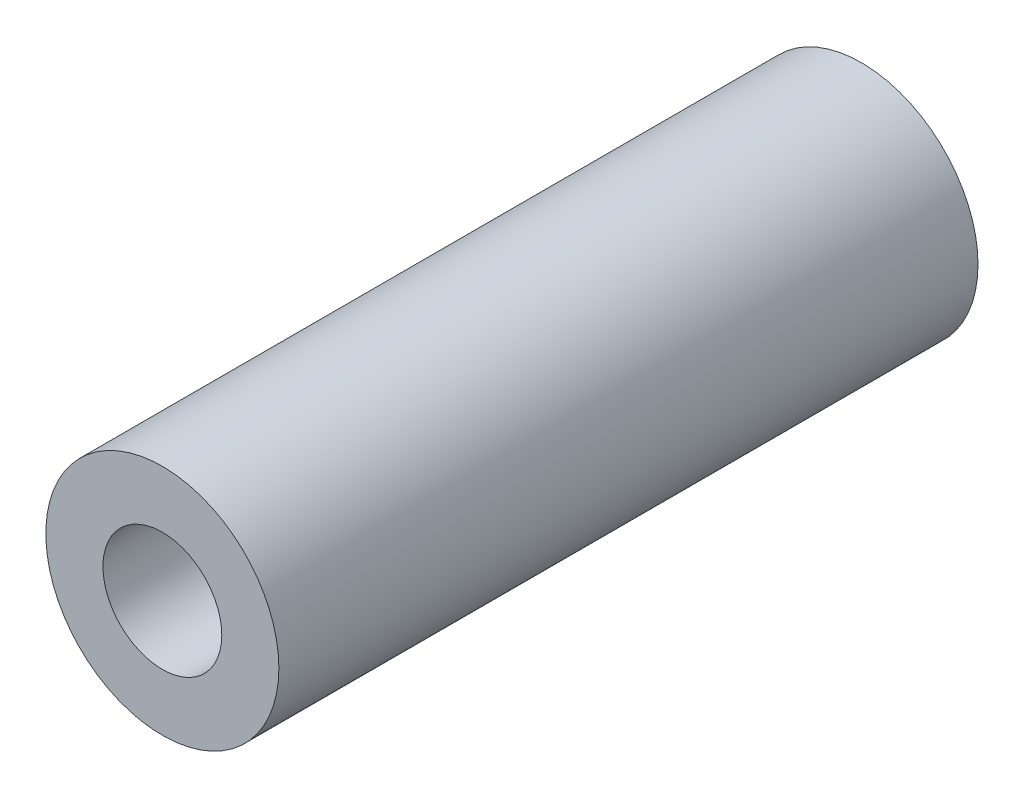
SolidWorks part; units mm, degrees
ref_plane "xy_plane" through (0, 0, 0) normal (0, 0, 1) x (1, 0, 0)
ref_plane "zx_plane" through (0, 0, 0) normal (0, 1, 0) x (1, 0, 0)
ref_plane "yz_plane" through (0, 0, 0) normal (1, 0, 0) x (0, 0, -1)
ref_axis "x_axis" through (-80.9, 0, 0) along (1, 0, 0)
ref_axis "y_axis" through (0, -50, 0) along (0, 1, 0)
ref_axis "z_axis" through (0, 0, -80.9) along (0, 0, 1)
ref_plane "xMid_plane" through (0, 0, 0) normal (1, 0, 0) x (0, 0, -1)
ref_plane "xMin_plane" through (-15, 0, 0) normal (1, 0, 0) x (0, 0, -1)
ref_plane "xMax_plane" through (15, 0, 0) normal (1, 0, 0) x (0, 0, -1)
ref_plane "yMid_plane" through (0, 0, 0) normal (0, 1, 0) x (1, 0, 0)
ref_plane "yMin_plane" through (0, -35, 0) normal (0, 1, 0) x (1, 0, 0)
ref_plane "yMax_plane" through (0, 35, 0) normal (0, 1, 0) x (1, 0, 0)
ref_plane "zMid_plane" through (0, 0, 0) normal (0, 0, 1) x (1, 0, 0)
ref_plane "zMin_plane" through (0, 0, -15) normal (0, 0, 1) x (1, 0, 0)
ref_plane "zMax_plane" through (0, 0, 15) normal (0, 0, 1) x (1, 0, 0)
sketch "projectionXy_sketch" plane through (0, 0, 0) normal (0, 0, 1) x (1, 0, 0)
  circle A0 centre (0, 0) radius 5
  dimension "D1" = 10
extrude "mainBody_extrude" add sketch "projectionXy_sketch" along normal up to surface (15 mm away) from surface up to plane "zMax_plane" starting at plane "zMin_plane"
sketch "bore_sketch" plane through (0, 0, 0) normal (0, 0, 1) x (1, 0, 0)
  circle A0 centre (0, 0) radius 2.55
  dimension "D1" = 5.1
extrude "Cut-Extrude1" cut sketch "bore_sketch" against normal through all both and the other way through all from surface starting at plane "zMid_plane"
equation "\"D1@zMin_plane\" = \"externalParameters.this.extentZ\" / 2"
equation "\"D1@zMax_plane\" = \"externalParameters.this.extentZ\" / 2"
equation "\"D1@bore_sketch\" = \"externalParameters.this.bore.diameter\""
equation "\"D1@projectionXy_sketch\"=\"externalParameters.this.outerDiameter\""
